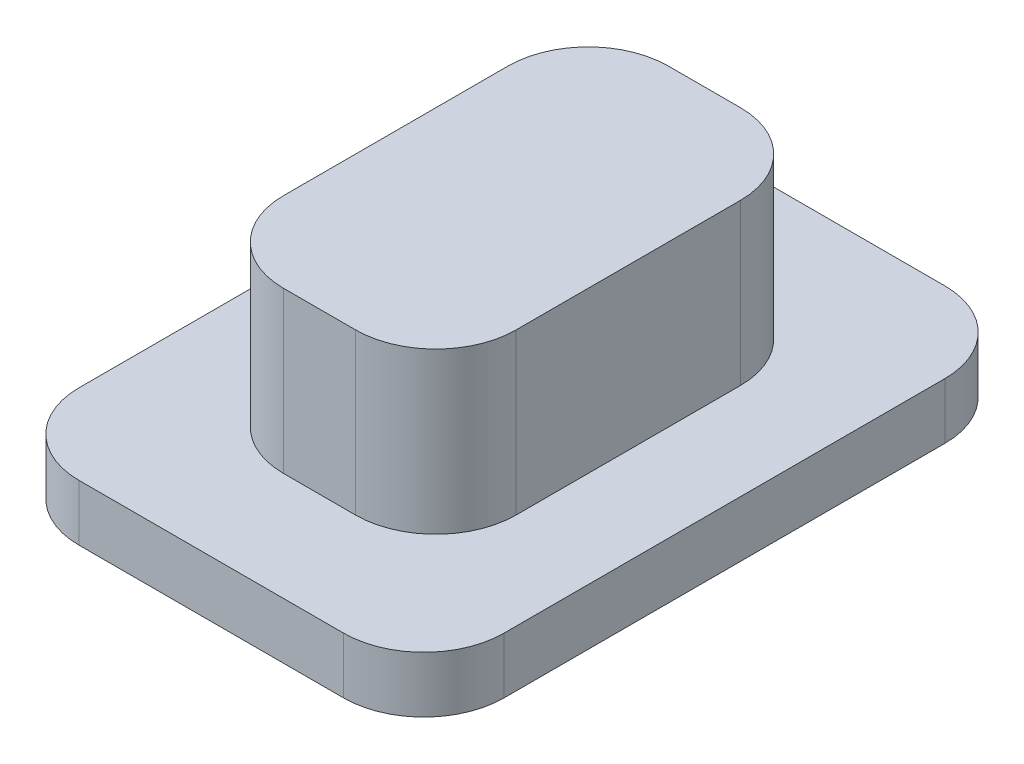
SolidWorks part; units mm, degrees
ref_plane "前视基准面" through (0, 0, 0) normal (0, 0, 1) x (1, 0, 0)
ref_plane "上视基准面" through (0, 0, 0) normal (0, 1, 0) x (1, 0, 0)
ref_plane "右视基准面" through (0, 0, 0) normal (1, 0, 0) x (0, 0, -1)
other "Configuration Table"
sketch "草图1" plane through (0, 0, 0) normal (0, 1, 0) x (1, 0, 0)
  line L5 (-2.1167, 3.333) -> (-0.4167, 0.133) construction
  line L6 (-2.1167, 0.133) -> (-0.4167, 3.333) construction
  line L7 (-1.7167, 4.133) -> (-0.8167, 4.133)
  line L8 (-2.7167, 3.133) -> (-2.7167, 0.333)
  line L9 (-1.7167, -0.667) -> (-0.8167, -0.667)
  line L10 (0.1833, 3.133) -> (0.1833, 0.333)
  line L11 (-2.7167, 4.133) -> (0.1833, -0.667) construction
  line L12 (-2.7167, -0.667) -> (0.1833, 4.133) construction
  line L13 (-2.9167, 5.483) -> (0.3833, 5.483)
  line L14 (-3.9167, 4.483) -> (-3.9167, -1.017)
  line L15 (-2.9167, -2.017) -> (0.3833, -2.017)
  line L16 (1.3833, 4.483) -> (1.3833, -1.017)
  line L17 (-3.9167, 5.483) -> (1.3833, -2.017) construction
  line L18 (-3.9167, -2.017) -> (1.3833, 5.483) construction
  arc A0 (-0.8167, -0.667) -> (0.1833, 0.333) centre (-0.8167, 0.333) ccw
  arc A1 (-2.7167, 0.333) -> (-1.7167, -0.667) centre (-1.7167, 0.333) ccw
  arc A2 (-0.8167, 4.133) -> (0.1833, 3.133) centre (-0.8167, 3.133) cw
  arc A3 (-1.7167, 4.133) -> (-2.7167, 3.133) centre (-1.7167, 3.133) ccw
  arc A4 (0.3833, -2.017) -> (1.3833, -1.017) centre (0.3833, -1.017) ccw
  arc A5 (-3.9167, -1.017) -> (-2.9167, -2.017) centre (-2.9167, -1.017) ccw
  arc A6 (0.3833, 5.483) -> (1.3833, 4.483) centre (0.3833, 4.483) cw
  arc A7 (-2.9167, 5.483) -> (-3.9167, 4.483) centre (-2.9167, 4.483) ccw
  point P0 (-1.2667, 1.733)
  point P5 (-1.2667, 1.733)
  point P22 (-1.2667, 1.733)
  dimension "D5" = 1
  dimension "D8" = 1
  dimension "D1" = 1.7
  dimension "D2" = 3.2
  dimension "D3" = 2.9
  dimension "D4" = 4.8
  dimension "D6" = 5.3
  dimension "D7" = 7.5
extrude "凸台-拉伸1" add sketch "草图1" along normal blind 0.7 contours L13 A7 L14 A5 L15 A4 L16 A6 A3 L7 A2 L10 A0 L9 A1 L8 region at (-1.2667, 0, -5.3912)
extrude "凸台-拉伸3" add sketch "草图1<6>" along normal blind 2.7 contours L7 A3 L8 A1 L9 A0 L10 A2 region at (-1.2667, 0, -1.733)
sketch "草图1<6>" plane through (0, 0, 0) normal (0, 1, 0) x (1, 0, 0) same geometry as "草图1"
